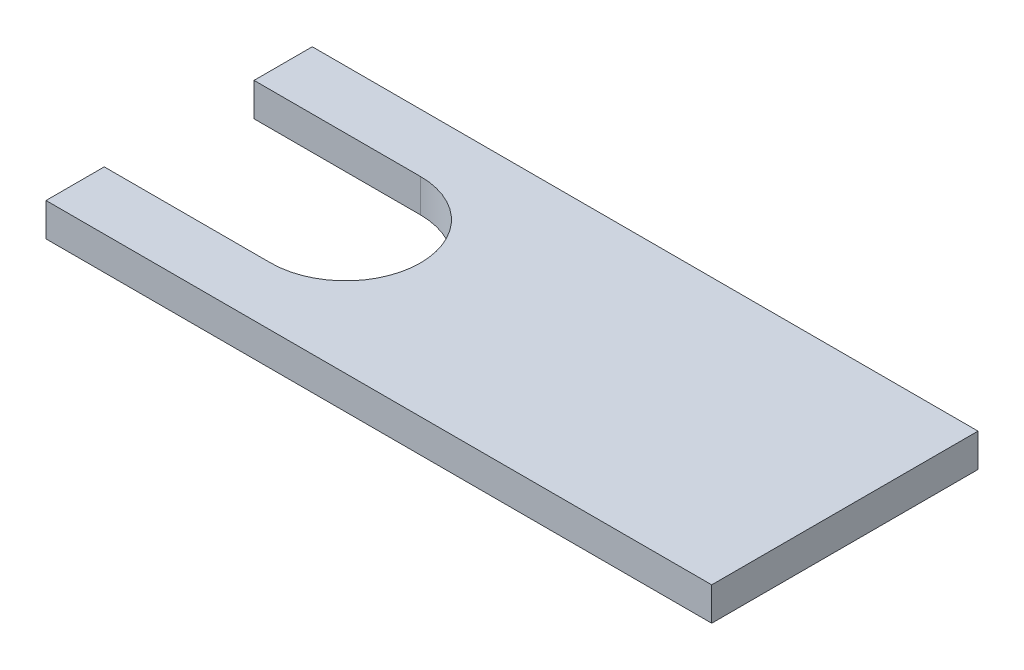
SolidWorks part; units mm, degrees
ref_plane "Front Plane" through (0, 0, 0) normal (0, 0, 1) x (1, 0, 0)
ref_plane "Top Plane" through (0, 0, 0) normal (0, 1, 0) x (1, 0, 0)
ref_plane "Right Plane" through (0, 0, 0) normal (1, 0, 0) x (0, 0, -1)
sketch "Sketch1" plane through (0, 0, 0) normal (0, 1, 0) x (1, 0, 0)
  line L0 (0, 0) -> (5, 0) construction
  line L1 (0, 2.25) -> (5, 2.25)
  line L2 (0, -2.25) -> (5, -2.25)
  line L3 (20, -4) -> (0, -4)
  line L4 (20, -4) -> (20, 4)
  line L5 (0, -4) -> (0, 4)
  line L6 (20, 4) -> (0, 4)
  line L7 (0, 0) -> (20, 0) construction
  line L8 (10, -4) -> (10, 4) construction
  arc A0 (0, 2.25) -> (0, -2.25) centre (0, 0) ccw
  arc A1 (5, -2.25) -> (5, 2.25) centre (5, 0) ccw
  point P2 (2.5, 0)
  point P8 (0, 0)
  point P9 (10, 0)
  point P10 (0, 0)
  dimension "D1" = 2.25
  dimension "D2" = 20
  dimension "D3" = 8
  dimension "D4" = 5
extrude "Boss-Extrude1" add sketch "Sketch1" along normal blind 1 contours A1 L2 L5 L3 L4 L6 L1 region at (11.5509, 0, 0)
